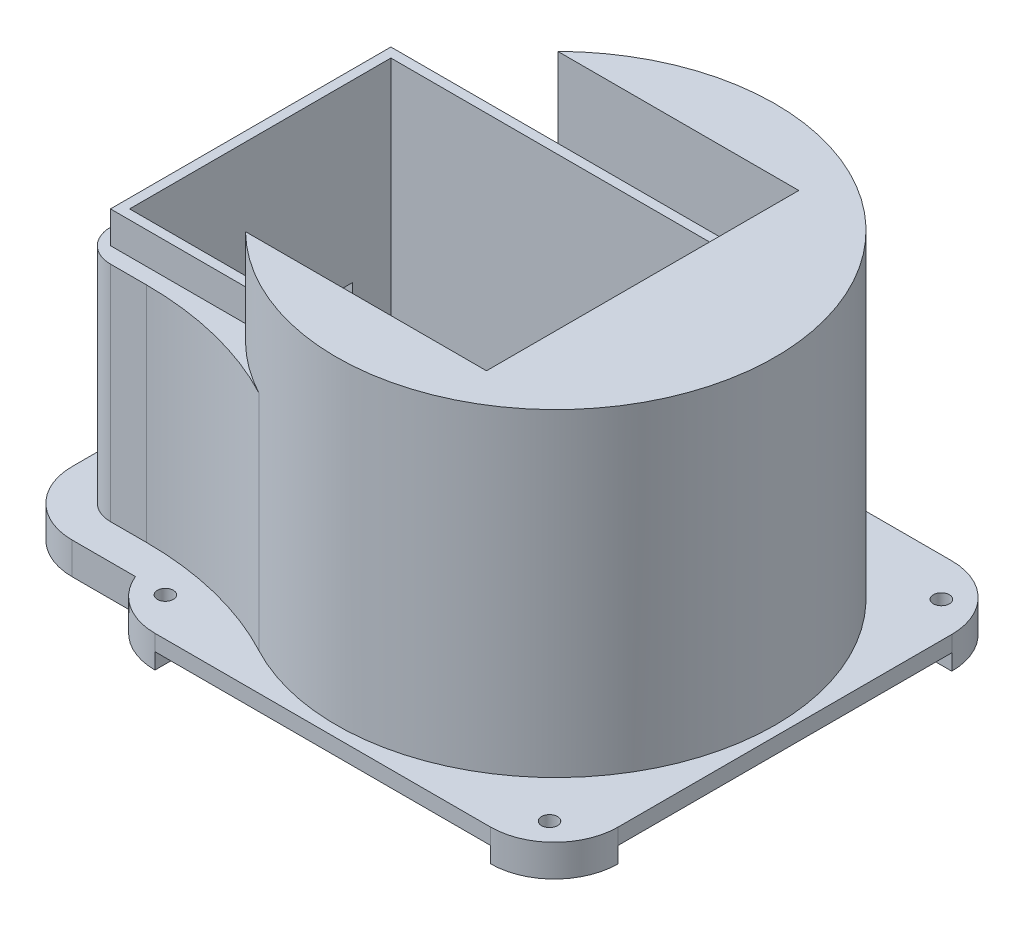
SolidWorks part; units mm, degrees
other "Cámara1"
other "Marca1"
sketch "Croquis31" plane through (-75, 105, 72.3604) normal (-0.3779, 0.832, 0.4063) x (0.3021, -0.304, 0.9035)
ref_plane "Alzado" through (0, 0, 0) normal (0, 0, 1) x (1, 0, 0)
ref_plane "Planta" through (0, 0, 0) normal (0, 1, 0) x (1, 0, 0)
ref_plane "Vista lateral" through (0, 0, 0) normal (1, 0, 0) x (0, 0, -1)
sketch "Croquis2" plane through (0, 0, 0) normal (0, 1, 0) x (1, 0, 0)
  line L1 (-59, 44) -> (59, 44)
  line L2 (-59, 44) -> (-59, -44)
  line L3 (-59, -44) -> (59, -44)
  line L4 (59, 44) -> (59, -44)
  line L5 (-59, 44) -> (59, -44) construction
  line L6 (-59, -44) -> (59, 44) construction
  point P0 (0, 0)
  dimension "D1" = 118
  dimension "D2" = 88
extrude "Saliente-Extruir1" add sketch "Croquis2" along normal blind 5
sketch "Croquis3" plane through (0, 5, 0) normal (0, 1, 0) x (1, 0, 0)
  line L1 (-56, 41) -> (56, 41)
  line L2 (-56, 41) -> (-56, -41)
  line L3 (-56, -41) -> (56, -41)
  line L4 (56, 41) -> (56, -41)
  line L5 (-56, 41) -> (56, -41) construction
  line L6 (-56, -41) -> (56, 41) construction
  line L7 (-59, -44) -> (59, -44)
  line L8 (-59, -44) -> (-59, 44)
  line L9 (-59, 44) -> (59, 44)
  line L10 (59, -44) -> (59, 44)
  line L11 (-59, -44) -> (59, 44) construction
  line L12 (-59, 44) -> (59, -44) construction
  point P0 (0, 0)
  point P6 (0, 0)
  dimension "D1" = 82
  dimension "D2" = 112
extrude "Saliente-Extruir2" add sketch "Croquis3" along normal blind 80
sketch "Croquis4" plane through (0, 0, 0) normal (0, -1, 0) x (1, 0, 0)
  line L1 (-75, 60) -> (75, 60)
  line L2 (-75, 60) -> (-75, -60)
  line L3 (-75, -60) -> (75, -60)
  line L4 (75, 60) -> (75, -60)
  line L5 (-75, 60) -> (75, -60) construction
  line L6 (-75, -60) -> (75, 60) construction
  point P0 (0, 0)
  dimension "D1" = 150
  dimension "D2" = 120
extrude "Saliente-Extruir3" add sketch "Croquis4" against normal blind 5
sketch "Croquis7" plane through (-59, 0, 0) normal (-1, 0, 0) x (0, 0, 1)
  line L0 (44, 85) -> (44, 5) construction
  line L1 (-44, 5) -> (44, 5)
  line L2 (-44, 5) -> (-44, 30)
  line L3 (-44, 30) -> (44, 30)
  line L4 (44, 5) -> (44, 30)
  line L5 (44, 5) -> (44, 13)
  line L7 (44, 13) -> (-44, 13)
  line L8 (44, 13) -> (44, 5)
  line L9 (44, 5) -> (-44, 5)
  line L10 (-44, 13) -> (-44, 5)
  line L11 (44, 30) -> (27, 30)
  line L12 (44, 30) -> (44, 13)
  line L13 (44, 13) -> (27, 13)
  line L14 (27, 30) -> (27, 13)
  line L15 (-44, 30) -> (-33, 30)
  line L16 (-44, 30) -> (-44, 13)
  line L17 (-44, 13) -> (-33, 13)
  line L18 (-33, 30) -> (-33, 13)
  dimension "D1" = 25
  dimension "D2" = 8
  dimension "D3" = 17
  dimension "D4" = 11
extrude "Cortar-Extruir3" cut sketch "Croquis7" against normal blind 5 contours L3 L18 L7 L14 region at (-59, 21.5, -3)
sketch "Croquis8" plane through (0, 0, -33) normal (0, 0, 1) x (1, 0, 0)
  line L1 (-56, 13) -> (-59, 13)
  line L2 (-56, 13) -> (-56, 30)
  line L3 (-56, 30) -> (-59, 30)
  line L4 (-59, 13) -> (-59, 30)
extrude "Saliente-Extruir4" add sketch "Croquis8" along normal blind 4
sketch "Croquis9" plane through (0, 0, 27) normal (0, 0, -1) x (-1, 0, 0)
  line L1 (56, 13) -> (59, 13)
  line L2 (56, 13) -> (56, 30)
  line L3 (56, 30) -> (59, 30)
  line L4 (59, 13) -> (59, 30)
extrude "Saliente-Extruir5" add sketch "Croquis9" along normal blind 7
sketch "Croquis10" plane through (0, 0, 44) normal (0, 0, 1) x (1, 0, 0)
  line L0 (-59, 85) -> (-59, 5) construction
  line L1 (-59, 75) -> (59, 75)
  line L2 (-59, 75) -> (-59, 70)
  line L3 (-59, 70) -> (59, 70)
  line L4 (59, 75) -> (59, 70)
  line L5 (59, 85) -> (59, 5) construction
  line L6 (-59, 85) -> (59, 85) construction
  dimension "D1" = 5
  dimension "D2" = 10
extrude "Saliente-Extruir6" add sketch "Croquis10" along normal blind 5
sketch "Croquis11" plane through (59, 0, 0) normal (1, 0, 0) x (0, 0, -1)
  line L0 (44, 85) -> (44, 5) construction
  line L1 (-49, 75) -> (44, 75)
  line L2 (-49, 75) -> (-49, 70)
  line L3 (-49, 70) -> (44, 70)
  line L4 (44, 75) -> (44, 70)
  dimension "D1" = 5
extrude "Saliente-Extruir7" add sketch "Croquis11" along normal blind 5
sketch "Croquis12" plane through (0, 0, -44) normal (0, 0, -1) x (-1, 0, 0)
  line L0 (59, 85) -> (59, 5) construction
  line L1 (-64, 75) -> (59, 75)
  line L2 (-64, 75) -> (-64, 70)
  line L3 (-64, 70) -> (59, 70)
  line L4 (59, 75) -> (59, 70)
  dimension "D1" = 5
extrude "Saliente-Extruir8" add sketch "Croquis12" along normal blind 5
sketch "Croquis13" plane through (-59, 0, 0) normal (-1, 0, 0) x (0, 0, 1)
  line L1 (-49, 75) -> (49, 75)
  line L2 (-49, 75) -> (-49, 70)
  line L3 (-49, 70) -> (49, 70)
  line L4 (49, 75) -> (49, 70)
extrude "Saliente-Extruir9" add sketch "Croquis13" along normal blind 5
sketch "Croquis16" plane through (0, 0, 0) normal (0, -1, 0) x (-1, 0, 0)
  line L0 (0, 0) -> (-152.7738, 0) construction
  line L2 (-75, 60) -> (-2.9727, 60)
  line L3 (-75, 60) -> (-75, -60)
  line L4 (-75, -60) -> (-2.9727, -60)
  line L7 (-59, 44) -> (16.215, 44)
  line L8 (-59, 44) -> (-59, -44)
  line L9 (-59, -44) -> (16.215, -44)
  arc A0 (16.215, 44) -> (16.215, -44) centre (-36.7401, 0) ccw
extrude "Saliente-Extruir11" add sketch "Croquis16" against normal blind 85 contours L0 A0 L3 | L3 L0 A0 | L8 L0 L3 A0 L9 | L0 L8 L7 A0 L3 | A0 L9 L8 L7 region at (60.0918, 0, 22) region at (67, 0, -1.0918) region at (87.5035, 0, 22.2832) region at (87.5035, 0, -22.2832)
sketch "Croquis18" plane through (0, 85, 0) normal (0, 1, 0) x (1, 0, 0)
  line L15 (-64, 49) -> (-8.4151, 49)
  line L16 (-64, 49) -> (-64, 44)
  line L17 (-64, 44) -> (-16.215, 44)
  line L19 (-64, -49) -> (-8.4151, -49)
  line L20 (-64, -49) -> (-64, -44)
  line L21 (-64, -44) -> (-16.215, -44)
  line L23 (-16.215, -44) -> (59, -44)
  line L25 (-8.4151, -49) -> (63.3611, -49)
  line L27 (-8.4151, 49) -> (63.3611, 49)
  line L29 (-16.215, 44) -> (59, 44)
  line L34 (59, 41) -> (59, -41)
  line L36 (59, -44) -> (59, 44)
  line L38 (64, -44) -> (64, 44)
  line L40 (64, -44) -> (64, -49)
  line L41 (64, -49) -> (63.3611, -49)
  line L43 (63.3611, 49) -> (64, 49)
  line L46 (64, 49) -> (64, 44)
  arc M24 (-16.215, -44) -> (-16.215, 44) centre (36.7401, 0) ccw
  dimension "D2" = 5
extrude "Cortar-Extruir4" cut sketch "Croquis18" along direction (0, -1, 0) on the side against the normal blind 10 contours L46 L43 L27 L29 L36 L34 L23 L25 L41 L40 L38 M24 region at (-10.0203, 85, -47.7336)
sketch "Croquis19" plane through (0, 5, 0) normal (0, 1, 0) x (1, 0, 0)
  line L0 (-64, -44) -> (-64, -49)
  line L1 (-16.215, -44) -> (-59, -44)
  line L3 (-8.4151, -49) -> (-64, -49)
  line L5 (-16.215, 44) -> (-59, 44)
  line L7 (-8.4151, 49) -> (-64, 49)
  line L10 (-59, 44) -> (-59, -44)
  line L12 (-64, 44) -> (-64, -44)
  line L13 (-64, -49) -> (-64, 49)
  line L15 (-59, 44) -> (59, 44) construction
  line L16 (-8.4151, 49) -> (3.5034, 49)
  line L18 (-16.215, 44) -> (3.5034, 44)
  line L19 (3.5034, 49) -> (3.5034, 44)
  line L20 (-59, -44) -> (59, -44) construction
  line L21 (-8.4151, -49) -> (4.2435, -49)
  line L23 (-16.215, -44) -> (4.2435, -44)
  line L24 (4.2435, -49) -> (4.2435, -44)
  arc M18 (2.9727, -60) -> (-16.215, -44) centre (36.7401, 0) cw
  line M19 (-16.215, -44) -> (-59, -44)
  line M20 (-59, -44) -> (-59, 44)
  line M21 (-59, 44) -> (-16.215, 44)
  arc M22 (-16.215, 44) -> (2.9727, 60) centre (36.7401, 0) cw
  dimension "D3" = 5
extrude "Saliente-Extruir12" add sketch "Croquis19" along normal blind 70 contours L3 L21 L16 L7 L13 L12 L0 M18 M19 M20 M21 M22 region at (-62.8888, 5, 0)
sketch "Croquis21" plane through (-56, 0, 0) normal (1, 0, 0) x (0, 0, -1)
  line L1 (29, 30) -> (-20, 30)
  line L2 (29, 30) -> (29, 13)
  line L3 (29, 13) -> (-20, 13)
  line L4 (-20, 30) -> (-20, 13)
extrude "Cortar-Extruir5" cut sketch "Croquis21" against normal blind 70
fillet "Redondeo4" radius 10 2 edges at (-64, 40, -49) (-64, 40, 49)
fillet "Redondeo5" radius 100 2 edges at (-11.6256, 40, -49) (-11.6256, 40, 49)
sketch "Croquis22" plane through (0, 85, 0) normal (0, 1, 0) x (1, 0, 0)
  line L0 (-11.6256, 49) -> (64, 49) construction
  line L1 (64, -49) -> (4.3158, -49)
  line L2 (64, -49) -> (64, 49)
  line L3 (64, 49) -> (4.3158, 49)
  line L6 (4.3158, 49) -> (-11.6256, 49)
  line L8 (4.3158, -49) -> (-11.6256, -49)
  arc A0 (-11.6256, -49) -> (-11.6256, 49) centre (36.7401, 0) ccw
  dimension "D1" = 68.8494
extrude "Saliente-Extruir13" add sketch "Croquis22" along normal blind 20
sketch "Croquis23" plane through (0, 0, 0) normal (0, -1, 0) x (-1, 0, 0)
  line L1 (-108.6447, -72.3604) -> (35.1645, -72.3604)
  line L2 (-108.6447, -72.3604) -> (-108.6447, 72.3604)
  line L3 (-108.6447, 72.3604) -> (35.1645, 72.3604)
  line L4 (35.1645, -72.3604) -> (35.1645, 72.3604)
  line L5 (-108.6447, -72.3604) -> (35.1645, 72.3604) construction
  line L6 (-108.6447, 72.3604) -> (35.1645, -72.3604) construction
  circle A0 centre (-36.7401, 0) radius 24.0043
extrude "Saliente-Extruir14" add sketch "Croquis23" against normal blind 5
sketch "Croquis25" plane through (0, 0, 0) normal (0, -1, 0) x (-1, 0, 0)
  line L0 (35.1645, -60) -> (35.1645, -72.3604)
  line L1 (75, -60) -> (35.1645, -60)
  line L2 (75, -60) -> (75, 60)
  line L3 (75, 60) -> (35.1645, 60)
  line L5 (-108.6447, 72.3604) -> (35.1645, 72.3604)
  line L6 (-108.6447, 72.3604) -> (-108.6447, -72.3604)
  line L7 (-108.6447, -72.3604) -> (35.1645, -72.3604)
  line L8 (35.1645, 72.3604) -> (35.1645, 60)
extrude "Saliente-Extruir15" add sketch "Croquis25" along normal blind 5
fillet "Redondeo9" radius 20 4 edges at (108.6447, 0, -72.3604) (108.6447, 0, 72.3604) (-35.1645, 0, 72.3604) (-35.1645, 0, -72.3604)
sketch "Croquis27" plane through (0, 0, -72.3604) normal (0, 0, -1) x (-1, 0, 0)
  line L0 (-88.6447, 5) -> (-88.6447, -5) construction
  line L1 (-88.6447, 0) -> (16.6811, 0)
  line L2 (-88.6447, 0) -> (-88.6447, -5)
  line L3 (-88.6447, -5) -> (16.6811, -5)
  line L4 (16.6811, 0) -> (16.6811, -5)
extrude "Cortar-Extruir7" cut sketch "Croquis27" against normal through all
sketch "Croquis28" plane through (108.6447, 0, 0) normal (1, 0, 0) x (0, 0, -1)
  line L0 (-52.3604, 5) -> (-52.3604, -5) construction
  line L1 (-52.3604, 0) -> (52.3604, 0)
  line L2 (-52.3604, 0) -> (-52.3604, -5)
  line L3 (-52.3604, -5) -> (52.3604, -5)
  line L4 (52.3604, 0) -> (52.3604, -5)
extrude "Cortar-Extruir8" cut sketch "Croquis28" against normal up to vertex (143.8091 mm away) up to point (-35.1645, -5, 60)
sketch "Croquis29" plane through (0, -5, 0) normal (0, -1, 0) x (-1, 0, 0)
  line L0 (-35.9818, -72.3604) -> (-35.9818, 72.3604) construction
  line L1 (16.6811, -72.3604) -> (-88.6447, -72.3604) construction
  line L2 (16.6811, 72.3604) -> (-88.6447, 72.3604) construction
  line L3 (35.1645, 0) -> (-108.6447, 0) construction
  line L4 (35.1645, 52.3604) -> (35.1645, -52.3604) construction
  line L5 (-108.6447, 52.3604) -> (-108.6447, -52.3604) construction
  circle A0 centre (-96.2568, -61.4823) radius 2.5
  circle A1 centre (-97.4641, 60.275) radius 2.5
  circle A2 centre (24.2932, 61.4823) radius 2.5
  circle A3 centre (25.5005, -60.275) radius 2.5
  point P14 (-35.9818, 0)
  point P24 (-35.9818, 0)
  dimension "D1" = 5
  dimension "D2" = 4
extrude "Cortar-Extruir9" cut sketch "Croquis29" against normal blind 10
fillet "Redondeo10" radius 20 2 edges at (-75, 0, -60) (-75, 0, 60)
sketch "Croquis30" plane through (56, 0, 0) normal (-1, 0, 0) x (0, 0, 1)
  line L0 (41, 85) -> (41, 5) construction
  line L1 (-41, 5) -> (41, 5)
  line L2 (-41, 5) -> (-41, 74.5907)
  line L3 (-41, 74.5907) -> (41, 74.5907)
  line L4 (41, 5) -> (41, 74.5907)
extrude "Cortar-Extruir10" cut sketch "Croquis30" against normal blind 30
